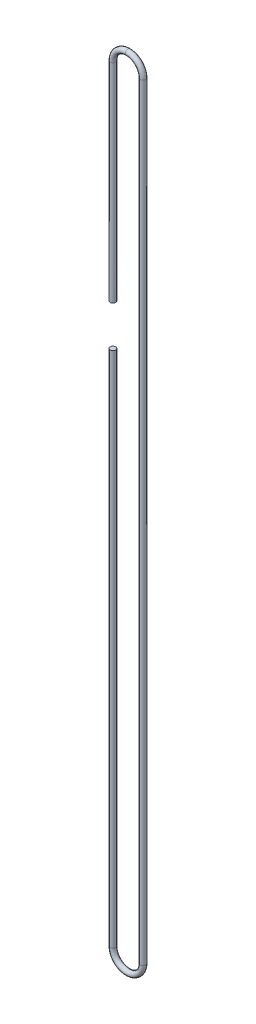
SolidWorks part; units mm, degrees
ref_plane "Front Plane" through (0, 0, 0) normal (0, 0, 1) x (1, 0, 0)
ref_plane "Top Plane" through (0, 0, 0) normal (0, 1, 0) x (1, 0, 0)
ref_plane "Right Plane" through (0, 0, 0) normal (1, 0, 0) x (0, 0, -1)
sketch "Sketch1" plane through (0, 0, 0) normal (0, 0, 1) x (1, 0, 0)
  line L0 (-17.4625, 889) -> (-17.4625, 0)
  line L1 (17.4625, 889) -> (17.4625, 0)
  circle A0 centre (0, 0) radius 17.4625 construction
  circle A1 centre (0, 889) radius 17.4625 construction
  arc A2 (-17.4625, 889) -> (17.4625, 889) centre (0, 889) cw
  arc A3 (-17.4625, 0) -> (17.4625, 0) centre (0, 0) ccw
  point P11 (0, 0)
  dimension "D2" = 17.4625
  dimension "D1" = 889
sketch "Sketch2" plane through (0, 0, 0) normal (1, 0, 0) x (0, 0, -1)
  line L0 (0, 906.4625) -> (0, 889) construction
  line L1 (0, 906.4625) -> (0, 889) construction
  circle A0 centre (0, 906.4625) radius 3.175
  point P1 (0, 0)
  point P6 (0, 0)
  point P7 (0, 905.9681)
  dimension "D1" = 6.35
sweep "Sweep1" add profiles "Sketch2" path "Sketch1"
sketch "Sketch3" plane through (0, 0, 0) normal (0, 0, 1) x (1, 0, 0)
  line L1 (-38.2585, 647.7) -> (-2.2207, 647.7)
  line L2 (-38.2585, 647.7) -> (-38.2585, 600.075)
  line L3 (-38.2585, 600.075) -> (-2.2207, 600.075)
  line L4 (-2.2207, 647.7) -> (-2.2207, 600.075)
  dimension "D1" = 47.625
  dimension "D2" = 241.3
extrude "Cut-Extrude1" cut sketch "Sketch3" against normal through all both and the other way through all
